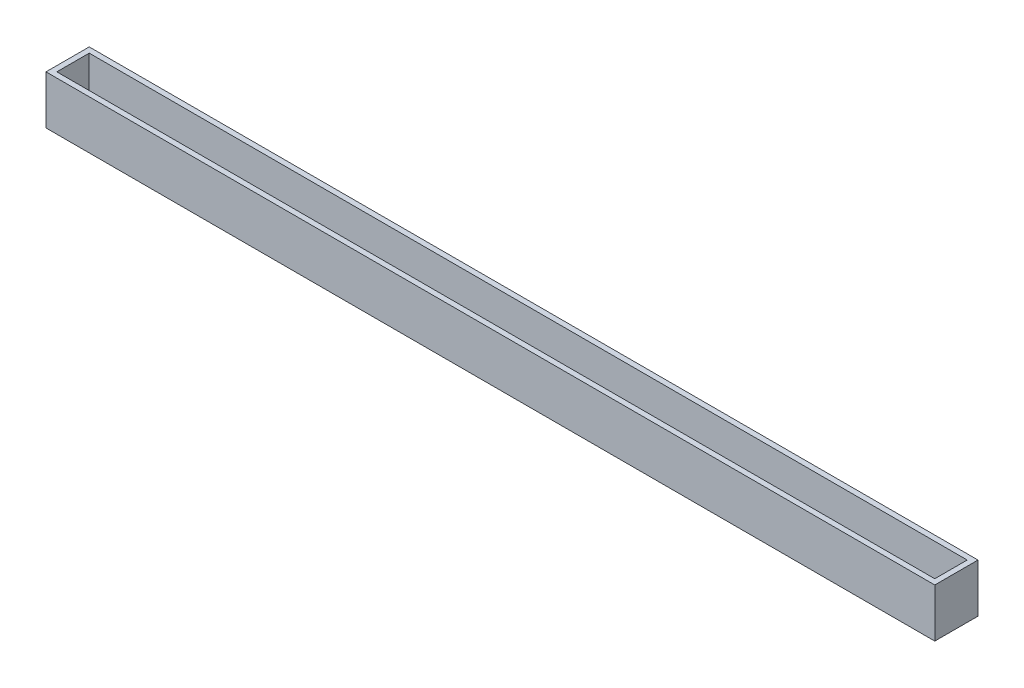
SolidWorks part; units mm, degrees
ref_plane "Спереди" through (0, 0, 0) normal (0, 0, 1) x (1, 0, 0)
ref_plane "Сверху" through (0, 0, 0) normal (0, 1, 0) x (1, 0, 0)
ref_plane "Справа" through (0, 0, 0) normal (1, 0, 0) x (0, 0, -1)
sketch "Эскиз1" plane through (0, 0, 0) normal (0, 1, 0) x (1, 0, 0)
  line L1 (-1645, -80) -> (1645, -80)
  line L2 (-1645, -80) -> (-1645, 80)
  line L3 (-1645, 80) -> (1645, 80)
  line L4 (1645, -80) -> (1645, 80)
  line L5 (-1645, -80) -> (1645, 80) construction
  line L6 (-1645, 80) -> (1645, -80) construction
  point P0 (0, 0)
  point P6 (1645, 0)
  dimension "D1" = 3290
  dimension "D2" = 160
extrude "Бобышка-Вытянуть1" add sketch "Эскиз1" along normal blind 180
shell "Оболочка1" thickness 20 removed face at (0, 180, 0)
